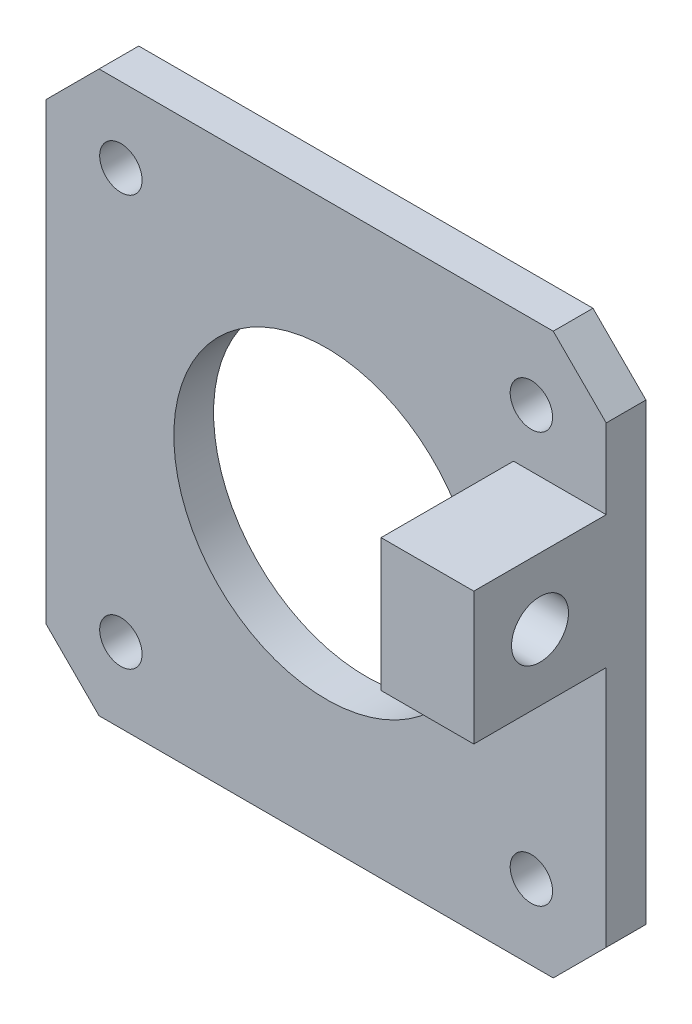
SolidWorks part; units mm, degrees
ref_plane "Front Plane" through (0, 0, 0) normal (0, 0, 1) x (1, 0, 0)
ref_plane "Top Plane" through (0, 0, 0) normal (0, 1, 0) x (1, 0, 0)
ref_plane "Right Plane" through (0, 0, 0) normal (1, 0, 0) x (0, 0, -1)
sketch "Croquis1" plane through (0, 0, 0) normal (0, 0, 1) x (1, 0, 0)
  line L1 (21.15, -17.15) -> (17.15, -21.15) construction
  line L2 (17.15, -21.15) -> (-17.15, -21.15) construction
  line L3 (-17.15, -21.15) -> (-21.15, -17.15) construction
  line L4 (-21.15, -17.15) -> (-21.15, 17.15) construction
  line L5 (17.15, 21.15) -> (16.7358, 20.15)
  line L6 (16.7358, 20.15) -> (20.15, 16.7358)
  line L7 (20.15, 16.7358) -> (21.15, 17.15)
  line L8 (21.15, 17.15) -> (17.15, 21.15)
  line L12 (21.15, 17.15) -> (17.15, 21.15)
  line L13 (-21.15, 17.15) -> (-17.15, 21.15) construction
  line L14 (-17.15, 21.15) -> (17.15, 21.15) construction
  line L15 (21.15, 17.15) -> (21.15, -17.15) construction
  line L16 (21.15, -17.15) -> (17.15, -21.15)
  line L17 (17.15, -21.15) -> (-17.15, -21.15)
  line L18 (-17.15, -21.15) -> (-21.15, -17.15)
  line L19 (-21.15, -17.15) -> (-21.15, 17.15)
  line L20 (-21.15, 17.15) -> (-17.15, 21.15)
  line L21 (-17.15, 21.15) -> (17.15, 21.15)
  line L22 (21.15, 17.15) -> (21.15, -17.15)
  circle A0 centre (0, 0) radius 11.5 construction
  circle A1 centre (0, 0) radius 11.5
  circle A12 centre (15.5, 15.5) radius 1.6
  circle A13 centre (15.5, 15.5) radius 1.6
  circle A27 centre (15.5, -15.5) radius 1.6
  circle A28 centre (15.5, -15.5) radius 1.6
  circle A30 centre (-15.5, -15.5) radius 1.6
  circle A31 centre (-15.5, -15.5) radius 1.6
  circle A32 centre (15.5, 15.5) radius 2.75 construction
  circle A33 centre (-15.5, 15.5) radius 1.6
  circle A34 centre (-15.5, 15.5) radius 1.6
  dimension "D6" = 5.5
  dimension "D1" = 0
  dimension "D2" = 0.35
  dimension "D3" = 0.35
  dimension "D4" = 0.35
  dimension "D5" = 0.35
extrude "Saliente-Extruir1" add sketch "Croquis1" along normal blind 3
sketch "Croquis2" plane through (21.15, 0, 0) normal (1, 0, 0) x (0, 0, -1)
  line L0 (-331, 6.25) -> (-331, 6.05) construction
  line L1 (-331, 6.25) -> (-331, 6.05)
  line L2 (-331, 6.15) -> (173.6057, 6.15) construction
  line L3 (-3, -17.15) -> (-3, 17.15) construction
  line L5 (-13, 11.15) -> (-3, 11.15)
  line L6 (-13, 11.15) -> (-13, 1.15)
  line L7 (-13, 1.15) -> (-3, 1.15)
  line L8 (-3, 11.15) -> (-3, 1.15)
  line L9 (-8, 1.15) -> (-8, 11.15) construction
  line L10 (-13, 6.15) -> (-3, 6.15) construction
  circle A0 centre (-8, 6.15) radius 2.15
  circle A1 centre (-8, 6.15) radius 3.5 construction
  point P4 (-8, 6.15)
  point P9 (-3, 6.15)
  point P16 (-331, 6.15)
  line M7 (-3, 17.15) -> (-3, -17.15)
  dimension "D3" = 4.3
  dimension "D4" = 7
  dimension "D1" = 10
  dimension "D2" = 10
extrude "Saliente-Extruir2" add sketch "Croquis2" against normal blind 7 contours L6 L7 L5 A0 M7 region at (21.15, 11.0086, 8)
